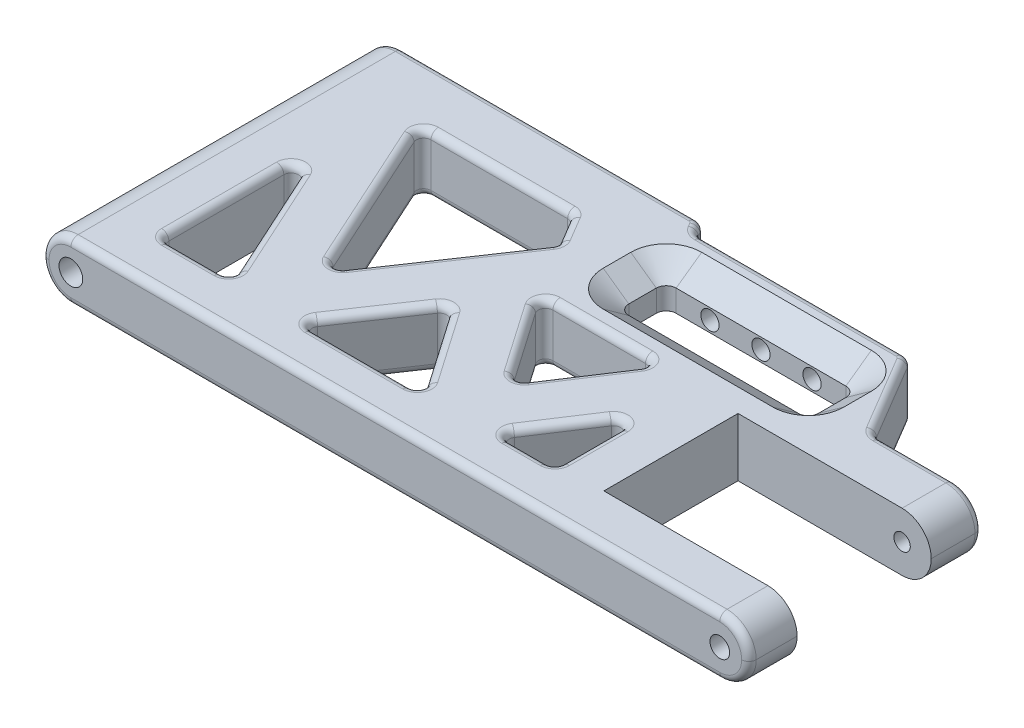
SolidWorks part; units mm, degrees
ref_plane "Plan de face" through (0, 0, 0) normal (0, 0, 1) x (1, 0, 0)
ref_plane "Plan de dessus" through (0, 0, 0) normal (0, 1, 0) x (1, 0, 0)
ref_plane "Plan de droite" through (0, 0, 0) normal (1, 0, 0) x (0, 0, -1)
sketch "Esquisse1" plane through (0, 0, 0) normal (0, 1, 0) x (1, 0, 0)
  line L0 (97, 2.25) -> (97, 9.25)
  line L1 (64.1189, -15.4942) -> (64.1189, -7.4672)
  line L2 (57.8567, -16.4942) -> (63.1189, -16.4942)
  line L3 (62.2826, -6.9189) -> (57.0204, -14.946)
  line L4 (43.7067, 1.2624) -> (50.247, -8.1781)
  line L5 (51.9053, -8.1568) -> (58.0771, 1.2578)
  line L6 (57.2269, 2.8318) -> (44.5287, 2.8318)
  line L7 (31.1749, -16.8354) -> (44.6031, -16.8354)
  line L8 (36.9746, -5.4608) -> (30.3462, -15.2758)
  line L9 (45.4251, -15.2659) -> (38.6254, -5.451)
  line L10 (11, -16.3074) -> (18.1973, -16.3074)
  line L11 (10, 0.4606) -> (10, -15.3074)
  line L12 (19.107, -14.8921) -> (11.9097, 0.8758)
  line L13 (15.043, 13.2774) -> (24.3579, -7.1299)
  line L14 (34.6936, 14.6926) -> (15.9527, 14.6926)
  line L15 (37.5907, 10.7692) -> (35.5536, 14.2029)
  line L17 (26.0964, -7.2744) -> (37.5594, 9.6993)
  line L19 (0, 22.75) -> (44.2586, 22.75)
  line L20 (0, 22.75) -> (0, -22.75)
  line L35 (97, -22.75) -> (0, -22.75)
  line L64 (45.4308, 22.0824) -> (45.7363, 21.5676)
  line L65 (46.9086, 20.9) -> (74.5358, 20.9)
  line L67 (48.8631, 15.4) -> (72.1369, 15.4)
  line L69 (47.5, 10.2631) -> (47.5, 14.0369)
  line L72 (72.1369, 8.9) -> (48.8631, 8.9)
  line L75 (73.5, 14.0369) -> (73.5, 10.2631)
  line L78 (75.7081, 20.2324) -> (81.8277, 9.9176)
  line L79 (83, 9.25) -> (97, 9.25)
  line L80 (97, -22.75) -> (97, -16.15)
  line L82 (70.5, 2.25) -> (70.5, -16.15)
  line L83 (97, 2.25) -> (70.5, 2.25)
  line L86 (70.5, -16.15) -> (97, -16.15)
  arc A0 (63.1189, -16.4942) -> (64.1189, -15.4942) centre (63.1189, -15.4942) ccw
  arc A1 (57.0204, -14.946) -> (57.8567, -16.4942) centre (57.8567, -15.4942) ccw
  arc A2 (64.1189, -7.4672) -> (62.2826, -6.9189) centre (63.1189, -7.4672) ccw
  arc A3 (50.247, -8.1781) -> (51.9053, -8.1568) centre (51.069, -7.6086) ccw
  arc A4 (58.0771, 1.2578) -> (57.2269, 2.8318) centre (57.2269, 1.8152) ccw
  arc A5 (44.5287, 2.8318) -> (43.7067, 1.2624) centre (44.5287, 1.8318) ccw
  arc A6 (44.6031, -16.8354) -> (45.4251, -15.2659) centre (44.6031, -15.8354) ccw
  arc A7 (30.3462, -15.2758) -> (31.1749, -16.8354) centre (31.1749, -15.8354) ccw
  arc A8 (38.6254, -5.451) -> (36.9746, -5.4608) centre (37.8034, -6.0205) ccw
  arc A9 (18.1973, -16.3074) -> (19.107, -14.8921) centre (18.1973, -15.3074) ccw
  arc A10 (10, -15.3074) -> (11, -16.3074) centre (11, -15.3074) ccw
  arc A11 (11.9097, 0.8758) -> (10, 0.4606) centre (11, 0.4606) ccw
  arc A12 (24.3579, -7.1299) -> (26.0964, -7.2744) centre (25.2677, -6.7147) ccw
  arc A13 (15.9527, 14.6926) -> (15.043, 13.2774) centre (15.9527, 13.6926) ccw
  arc A14 (35.5536, 14.2029) -> (34.6936, 14.6926) centre (34.6936, 13.6926) ccw
  arc A16 (37.5594, 9.6993) -> (37.5907, 10.7692) centre (36.7307, 10.2589) ccw
  arc A45 (45.4308, 22.0824) -> (44.2586, 22.75) centre (44.2586, 21.3869) ccw
  arc A46 (45.7363, 21.5676) -> (46.9086, 20.9) centre (46.9086, 22.2631) ccw
  arc A47 (48.8631, 15.4) -> (47.5, 14.0369) centre (48.8631, 14.0369) ccw
  arc A48 (47.5, 10.2631) -> (48.8631, 8.9) centre (48.8631, 10.2631) ccw
  arc A49 (73.5, 14.0369) -> (72.1369, 15.4) centre (72.1369, 14.0369) ccw
  arc A50 (72.1369, 8.9) -> (73.5, 10.2631) centre (72.1369, 10.2631) ccw
  arc A51 (75.7081, 20.2324) -> (74.5358, 20.9) centre (74.5358, 19.5369) ccw
  arc A52 (81.8277, 9.9176) -> (83, 9.25) centre (83, 10.6131) ccw
  point P48 (37.1982, 11.344)
  point P52 (37.5907, 10.8676)
  point P63 (36.3382, 10.9205)
  dimension "D4" = 1
  dimension "D1" = 97
  dimension "D2" = 45.5
  dimension "D3" = 32
  dimension "D5" = 26.5
  dimension "D6" = 8
  dimension "D7" = 8
  dimension "D8" = 8
  dimension "D9" = 43.65
  dimension "D10" = 7
  dimension "D11" = 6.6
  dimension "D12" = 8
  dimension "D13" = 2.65
  dimension "D14" = 8.4642
  dimension "D15" = 14
  dimension "D16" = 27.6273
  dimension "D17" = 10
  dimension "D18" = 6.5
  dimension "D19" = 26
  dimension "D20" = 23.5
  dimension "D21" = 5.5
extrude "Boss.-Extru.1" add sketch "Esquisse1" along normal blind 4 and the other way blind 4
fillet "Congé1" radius 4 6 edges at (0, 4, 0) (97, -4, -5.75) (97, -4, 19.45) (97, 4, 19.45) (97, 4, -5.75) (0, -4, 0)
fillet "Congé2" radius 1 86 edges at (50.8778, -4, -2.8318) (54.9912, 4, 3.4495) (50.8778, 4, -2.8318) (48.5, 4, 22.75) (95.8284, 2.8284, 22.75) (95.8284, -2.8284, 22.75) (48.5, -4, 22.75) (1.1716, -2.8284, 22.75) (1.1716, -2.8284, -22.75) (24.1293, -4, -22.75) (44.9331, -4, -22.5714) (45.5836, -4, -21.825) (46.2341, -4, -21.0786) (60.7222, -4, -20.9) (75.2103, -4, -20.7214) (78.7679, -4, -15.075) (82.3255, -4, -9.4286) (88, -4, -9.25) (95.8284, -2.8284, -9.25) (95.8284, 2.8284, -9.25) (88, 4, -9.25) (82.3255, 4, -9.4286) (78.7679, 4, -15.075) (75.2103, 4, -20.7214) (60.7222, 4, -20.9) (46.2341, 4, -21.0786) (45.5836, 4, -21.825) (44.9331, 4, -22.5714) (24.1293, 4, -22.75) (54.9912, -4, 3.4495) (14.5987, 4, 16.3074) (1.1716, 2.8284, 22.75) (1.1716, 2.8284, -22.75) (51.0818, -4, 8.6085) (46.9768, -4, 3.4578) (43.6428, -4, -2.2958) (58.1214, -4, -2.2983) (10.2929, 4, 16.0145) (10, 4, 7.4234) (10.7875, 4, -1.4377) (15.5084, 4, 7.0082) (19.0385, 4, 15.8481) (63.826, 4, 16.2013) (60.4878, 4, 16.4942) (56.9769, 4, 15.9695) (59.6515, 4, 10.9325) (63.405, 4, 6.509) (45.489, 4, 16.2994) (37.889, 4, 16.8354) (30.2918, 4, 16.3046) (33.6604, 4, 10.3683) (37.7974, 4, 5.0205) (51.0818, 4, 8.6085) (46.9768, 4, 3.4578) (43.6428, 4, -2.2958) (58.1214, 4, -2.2983) (25.1849, 4, 7.7113) (19.7005, 4, -3.0737) (15.1115, 4, -14.2334) (25.3231, 4, -14.6926) (35.1884, 4, -14.5616) (36.5722, 4, -12.486) (37.7303, 4, -10.2297) (63.405, -4, 6.509) (64.1189, -4, 11.4807) (63.826, -4, 16.2013) (60.4878, -4, 16.4942) (56.9769, -4, 15.9695) (45.489, -4, 16.2994) (37.889, -4, 16.8354) (30.2918, -4, 16.3046) (33.6604, -4, 10.3683) (37.7974, -4, 5.0205) (25.1849, -4, 7.7113) (19.7005, -4, -3.0737) (15.1115, -4, -14.2334) (25.3231, -4, -14.6926) (35.1884, -4, -14.5616) (36.5722, -4, -12.486) (37.7303, -4, -10.2297) (64.1189, 4, 11.4807) (42.0252, 4, 10.3585) (31.8279, 4, -1.2125) (59.6515, -4, 10.9325) (42.0252, -4, 10.3585) (31.8279, -4, -1.2125)
chamfer "Chanfrein2" distance 3.5 distance2 2.5 8 edges at (60.5, 4, -8.9) (73.1008, 4, -9.2992) (47.8992, 4, -9.2992) (73.5, 4, -12.15) (47.5, 4, -12.15) (73.1008, 4, -15.0008) (47.8992, 4, -15.0008) (60.5, 4, -15.4) first distance on face at (61.4572, 4, 13.0438)
chamfer "Chanfrein3" distance 2.5 distance2 3.5 8 edges at (60.5, -4, -8.9) (73.1008, -4, -9.2992) (47.8992, -4, -9.2992) (73.5, -4, -12.15) (47.5, -4, -12.15) (73.1008, -4, -15.0008) (47.8992, -4, -15.0008) (60.5, -4, -15.4) first distance on face at (60.5, -1.25, -8.9) first distance on face at (72.9596, -1.25, -9.4404) first distance on face at (48.0404, -1.25, -9.4404) first distance on face at (73.5, -1.25, -12.15) first distance on face at (47.5, -1.25, -12.15) first distance on face at (72.9596, -1.25, -14.8596) first distance on face at (48.0404, -1.25, -14.8596) first distance on face at (60.5, -1.25, -15.4)
sketch "Esquisse6" plane through (0, 0, 0) normal (0, 0, 1) x (1, 0, 0)
  circle A1 centre (93, 0) radius 1.125
  dimension "D1" = 2.25
extrude "Enlèv. mat.-Extru.1" cut sketch "Esquisse6" against normal offset from surface 1 and the other way through all up to face at (89.8485, 0, -9.25)
sketch "Esquisse14" plane through (0, 0, 0) normal (0, 0, 1) x (1, 0, 0)
  line L0 (0, 0) -> (44.2586, 0) construction
  circle A0 centre (4, 0) radius 1.625
  arc A2 (4, 4) -> (0, 0) centre (4, 0) ccw construction
  dimension "D1" = 3.25
extrude "Enlèv. mat.-Extru.2" cut sketch "Esquisse14" against normal through all and the other way through all
hole_wizard "Trou taraudé M31" positions "Esquisse8" profile "Esquisse7" tap size "M3" standard "ISO"
sketch "Esquisse8" plane through (0, 0, -20.9) normal (0, 0, -1) x (-1, 0, 0)
  line L0 (-72.1369, 1.5) -> (-48.8631, 1.5) construction
  point P0 (-60.5, 0)
  point P2 (-53.5, 0)
  point P4 (-67.5, 0)
  point P8 (-60.5, 1.5)
  dimension "D1" = 7
  dimension "D2" = 7
sketch "Esquisse7" plane through (60.5, 0, -20.9) normal (1, 0, 0) x (0, 1, 0)
  line L0 (0, 0) -> (0, 16.7511)
  line L1 (0, 16.7511) -> (1.25, 16)
  line L2 (1.25, 16) -> (1.25, 0)
  line L5 (1.25, 0) -> (0, 0)
  line L10 (0, 16.7511) -> (-1.25, 16) construction
  line L11 (0, -6.35) -> (0, 107.95) construction
  dimension "Diamètre du trou pour taraudage" = 2.5
  dimension "Profondeur du trou pour taraudage" = 16
  dimension "Angle de pointe" = 118
cosmetic thread "Filetage de perçage1" parameters "D1"=16, "D2"=3
cosmetic thread "Filetage de perçage2" parameters "D1"=16, "D2"=3
cosmetic thread "Filetage de perçage3" parameters "D1"=16, "D2"=3
hole_wizard "Trou pour taraudage pour trou taraudé M31" positions "Esquisse11" profile "Esquisse12" hole size "M3" standard "ISO"
sketch "Esquisse11" plane through (0, 0, 22.75) normal (0, 0, 1) x (1, 0, 0)
  point P0 (93, 0)
sketch "Esquisse12" plane through (93, 0, 22.75) normal (1, 0, 0) x (0, -1, 0)
  line L0 (0, 0) -> (0, 3.8112)
  line L1 (0, 3.8112) -> (1.35, 3)
  line L2 (1.35, 3) -> (1.35, 0)
  line L5 (1.35, 0) -> (0, 0)
  line L10 (0, 3.8112) -> (-1.35, 3) construction
  line L11 (0, -6.35) -> (0, 107.95) construction
  dimension "Diamètre du perçage" = 2.7
  dimension "Profondeur du perçage" = 3
  dimension "Angle de pointe" = 118
